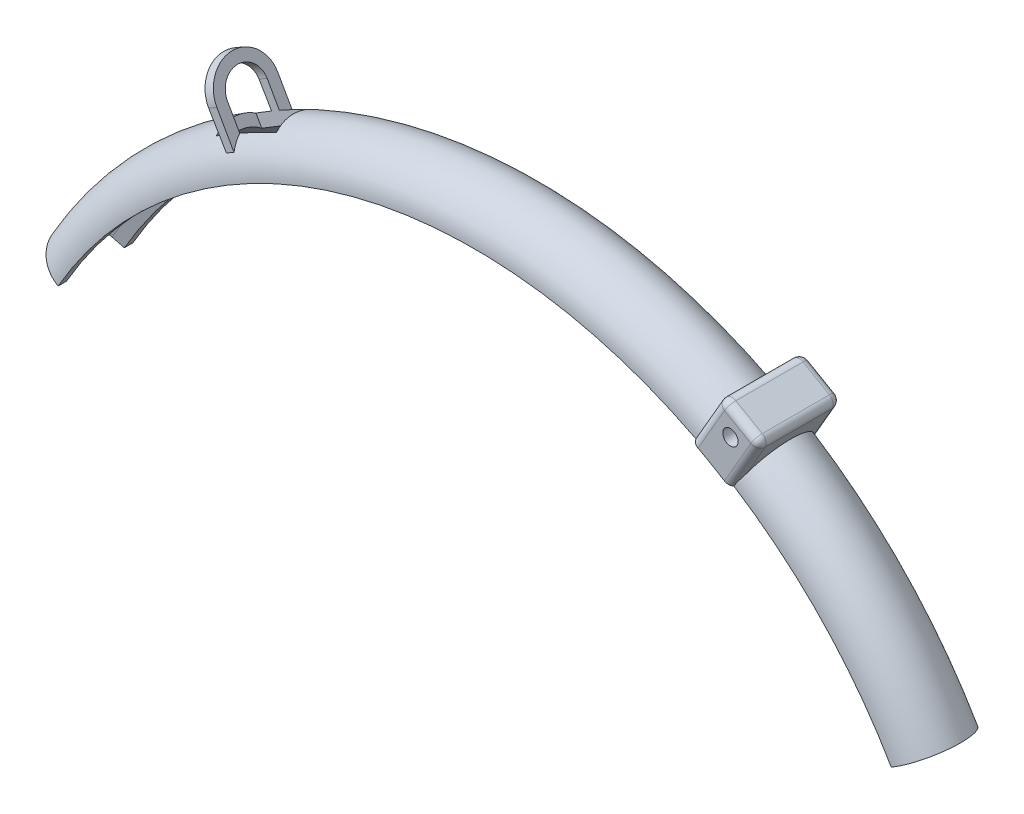
SolidWorks part; units mm, degrees
material "5052-H32"
ref_plane "Front Plane" through (0, 0, 0) normal (0, 0, 1) x (1, 0, 0)
ref_plane "Top Plane" through (0, 0, 0) normal (0, 1, 0) x (1, 0, 0)
ref_plane "Right Plane" through (0, 0, 0) normal (1, 0, 0) x (0, 0, -1)
sketch "Sketch1" plane through (0, 0, 0) normal (1, 0, 0) x (0, 0, -1)
  line L0 (25.4655, 0) -> (-25.4655, 0) construction
  line L1 (0, 31.55) -> (0, 0) construction
  line L2 (-1.9, 31.55) -> (-2.45, 31.55)
  line L3 (1.9, 31.55) -> (2.45, 31.55)
  line L6 (-1.9, 31.55) -> (-1.7326, 32.3)
  line L8 (1.9, 31.55) -> (1.7326, 32.3)
  line L9 (-1.9, 31.55) -> (1.9, 31.55) construction
  arc A0 (-2.45, 31.55) -> (2.45, 31.55) centre (0, 31.55) cw
  arc A5 (1.7326, 32.3) -> (1.6921, 32.45) centre (0, 31.9132) ccw
  arc A6 (-1.6921, 32.45) -> (1.6921, 32.45) centre (0, 31.2063) cw
  arc A7 (-1.6921, 32.45) -> (-1.7326, 32.3) centre (0, 31.9132) ccw
  point P4 (0, 0)
  point P16 (0, 31.55)
  point P17 (-2.6269, 31.2579)
  point P28 (0, 34)
  dimension "D2" = 2.45
  dimension "D8" = 2.1
  dimension "D6" = 34
  dimension "D1" = 0.55
  dimension "D3" = 0.75
  dimension "D7" = 0.9
  dimension "D4" = 77.414
  dimension "D5" = 77.414
revolve "Revolve1" add sketch "Sketch1" angle 120 mid plane about L0
sketch "Sketch3" plane through (0, 0, 0) normal (0, 0, 1) x (1, 0, 0)
  line L0 (0, 0) -> (17.5, 30.3109)
  line L1 (-17.5, 30.3109) -> (-32.9639, 21.3828) construction
  line L3 (0, 0) -> (-26.7986, 0) construction
  line L4 (0, 0) -> (-17.5, 30.3109)
  dimension "D2" = 35
  dimension "D3" = 60
  dimension "D1" = 120
ref_plane "Plane2" through (17.5, 30.3109, 0) normal (0.5, 0.866, 0) x (0.866, -0.5, 0)
sketch "Sketch4" plane through (17.5, 30.3109, 0) normal (0.5, 0.866, 0) x (0.866, -0.5, 0)
  line L0 (1.5, 2.7) -> (-1.5, 2.7)
  line L5 (-1.5, 2.7) -> (-1.5, -2.7)
  line L6 (-1.5, -2.7) -> (1.5, -2.7)
  line L7 (1.5, -2.7) -> (1.5, 2.7)
  line L8 (1.5, 0) -> (-1.5, 0) construction
  line L9 (0, 2.7) -> (0, -2.7) construction
  line L11 (-31.55, 2.45) -> (15.775, 2.45) construction
  point P9 (0, 0)
  dimension "D1" = 0.25
  dimension "D3" = 3
extrude "Boss-Extrude6" add sketch "Sketch4" against normal up to surface (3.9857 mm away) from offset 0.5 up to face at (0, 23.6625, 2.175)
fillet "Fillet1" radius 0.5 8 edges at (17.75, 30.7439, 2.7) (16.451, 31.4939, 0) (17.75, 30.7439, -2.7) (19.049, 29.9939, 0) (15.4545, 29.7681, 2.7) (18.0526, 28.2681, 2.7) (15.4545, 29.7681, -2.7) (18.0526, 28.2681, -2.7)
sketch "Sketch14" plane through (0, 0, 0) normal (0, 0, 1) x (1, 0, 0)
  line L1 (17.025, 29.4882) -> (15.775, 27.3231) construction
  line L2 (16.634, 30.8109) -> (14.901, 27.8094) construction
  circle A0 centre (17.025, 29.4882) radius 0.5
  arc A1 (16.6331, 26.8094) -> (14.901, 27.8094) centre (0, 0) ccw construction
  dimension "D2" = 1
  dimension "D1" = 2.5
extrude "Cut-Extrude3" cut sketch "Sketch14" against normal through all both and the other way through all
ref_plane "Plane3" through (-17.5, 30.3109, 0) normal (-0.5, 0.866, 0) x (0.866, 0.5, 0)
ref_plane "Plane5" through (-17.5, 30.3109, 0) normal (-0.866, -0.5, 0) x (0, 0, 1)
sketch "Sketch15" plane through (-17.5, 30.3109, 0) normal (-0.866, -0.5, 0) x (0, 0, 1)
  line L0 (-2, -3.5) -> (-1.3, -3.5)
  line L1 (-1.3, -3.5) -> (-1.3, 0.25)
  line L2 (1.3, 0.25) -> (1.3, -3.5)
  line L3 (1.3, -3.5) -> (2, -3.5)
  line L4 (2, -3.5) -> (2, 0.25)
  line L5 (-2, 0.25) -> (-2, -3.5)
  line L6 (0, -35) -> (0, 0) construction
  line L9 (-5.285, -35) -> (5.285, -35) construction
  line L10 (0, -35) -> (0, 0.25) construction
  arc A0 (-1.3, 0.25) -> (1.3, 0.25) centre (0, 0.25) cw
  arc A1 (2, 0.25) -> (-2, 0.25) centre (0, 0.25) ccw
  dimension "D1" = 2
  dimension "D2" = 0.7
  dimension "D3" = 31.5
  dimension "D4" = 3.75
revolve "Revolve2" add sketch "Sketch15" angle 1 mid plane about L9
sketch "Sketch6" plane through (-17.5, 30.3109, 0) normal (-0.5, 0.866, 0) x (0.866, 0.5, 0)
  line L0 (-1.5, 0) -> (3, 0) construction
  line L1 (-1.5, -1.3) -> (3, -1.3)
  line L2 (-1.5, -1.3) -> (-1.5, 1.3)
  line L3 (-1.5, 1.3) -> (3, 1.3)
  line L7 (3, 1.3) -> (3, -1.3)
  line L8 (-0.2934, 1.3) -> (-0.3076, 1.3) construction
  point P0 (0, 0)
  dimension "D3" = 3
  dimension "D1" = 2.6
  dimension "D2" = 1.5
extrude "Cut-Extrude6" cut sketch "Sketch6" against normal through all
sketch "Sketch17" plane through (0, 0, 0) normal (-0.5, -0.866, 0) x (0.866, -0.5, 0)
  line L5 (-31.55, -1.9) -> (-31.55, -2.45)
  line L6 (-32.3, -1.7326) -> (-31.55, -1.9)
  line L7 (-31.55, 1.9) -> (-32.3, 1.7326)
  line L8 (-32.3, -1.7326) -> (-31.55, -1.9)
  line L9 (-31.55, 1.9) -> (-32.3, 1.7326)
  line L10 (-31.55, -2.45) -> (-31.2063, -2.45)
  line L11 (-31.2063, -2.45) -> (-31.2063, 2.45)
  line L12 (-31.2063, 2.45) -> (-31.55, 2.45)
  line L13 (-31.55, 2.45) -> (-31.55, 1.9)
  arc A14 (-32.45, -1.6921) -> (-32.3, -1.7326) centre (-31.9132, 0) ccw
  arc A15 (-32.3, 1.7326) -> (-32.45, 1.6921) centre (-31.9132, 0) ccw
  arc A16 (-32.45, 1.6921) -> (-32.45, -1.6921) centre (-31.2063, 0) ccw
  arc A17 (-32.45, -1.6921) -> (-32.3, -1.7326) centre (-31.9132, 0) ccw
  arc A18 (-32.3, 1.7326) -> (-32.45, 1.6921) centre (-31.9132, 0) ccw
  arc A19 (-32.45, 1.6921) -> (-32.45, -1.6921) centre (-31.2063, 0) ccw
  dimension "D1" = 0
revolve "Cut-Revolve5" cut sketch "Sketch17" angle 360 about L9
equation "\"D6@Sketch1\"=34"
equation "\"D2@Sketch3\"= \"D6@Sketch1\" + 1"
equation "\"D3@Sketch15\"=\"D6@Sketch1\"-2.5"
